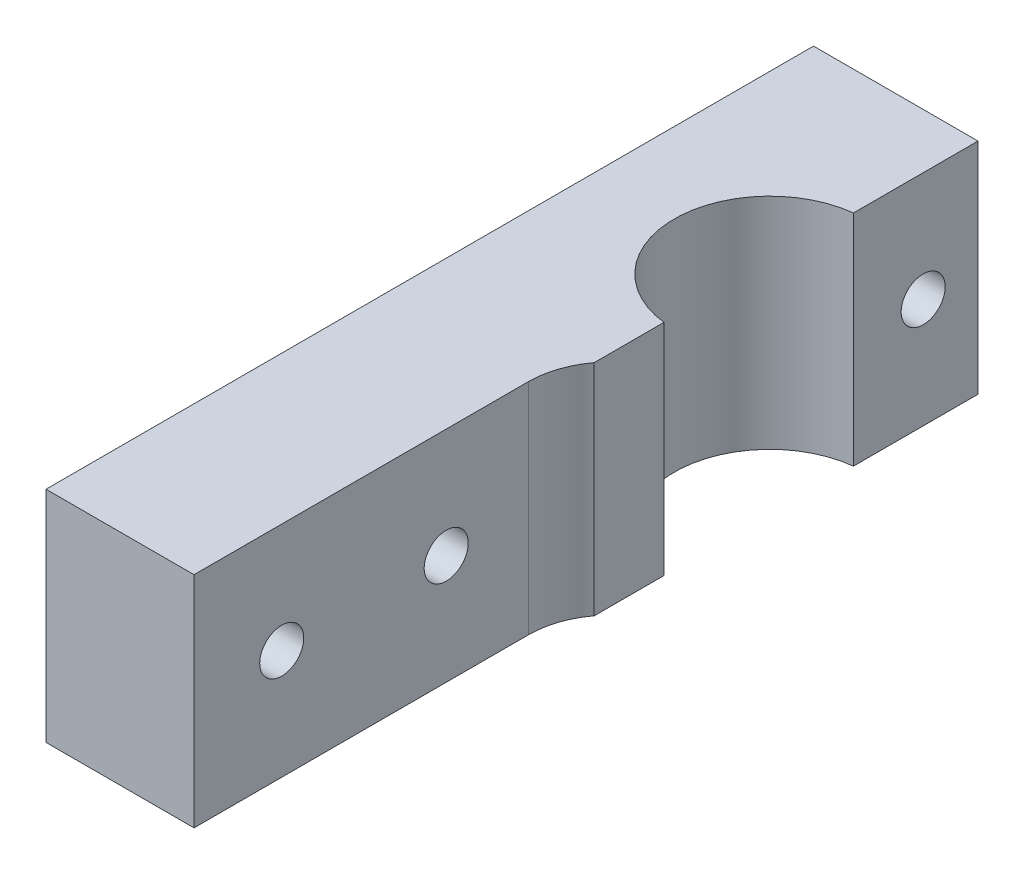
SolidWorks part; units mm, degrees
ref_plane "Front" through (0, 0, 0) normal (0, 0, 1) x (1, 0, 0)
ref_plane "Top" through (0, 0, 0) normal (0, 1, 0) x (1, 0, 0)
ref_plane "Right" through (0, 0, 0) normal (1, 0, 0) x (0, 0, -1)
sketch "Sketch1" plane through (0, 0, 0) normal (0, 1, 0) x (1, 0, 0)
  line L0 (-1.27, 10.9758) -> (-1.27, 25.4)
  line L1 (-1.27, 25.4) -> (-20.32, 25.4)
  line L2 (-1.27, 25.4) -> (-1.27, -63.5) construction
  line L3 (-1.27, -63.5) -> (-20.32, -63.5)
  line L4 (-20.32, 25.4) -> (-20.32, -63.5)
  line L5 (-1.27, -10.9758) -> (-1.27, -63.5)
  arc A0 (-1.27, 10.9758) -> (-1.27, -10.9758) centre (0, 0) ccw
  circle A1 centre (0, 0) radius 11.049 construction
  dimension "D2" = 22.098
  dimension "D1" = 25.4
  dimension "D3" = 19.05
  dimension "D4" = 1.27
  dimension "D5" = 63.5
extrude "Boss-Extrude1" add sketch "Sketch1" along normal mid plane 25.4
sketch "Sketch4" plane through (-20.32, 0, 0) normal (-1, 0, 0) x (0, 0, 1)
  line L0 (63.5, 12.7) -> (63.5, -12.7) construction
  point P0 (-19.05, 0)
  point P1 (34.29, 0)
  point P2 (53.34, 0)
  dimension "D1" = 19.05
  dimension "D2" = 10.16
  dimension "D3" = 19.05
hole_wizard "CBORE for #10 Binding Head Machine Screw1" positions "Sketch5" profile "Sketch6" counterbore size "#10" standard "ANSI Inch"
sketch "Sketch5" plane through (-20.32, 0, 0) normal (-1, 0, 0) x (0, 0, 1)
  point P0 (-19.05, 0)
  point P3 (34.29, 0)
  point P6 (53.34, 0)
sketch "Sketch6" plane through (-20.32, 0, -19.05) normal (0, 1, 0) x (0, 0, 1)
  line L0 (0, 0) -> (0, 509.5338)
  line L1 (0, 509.5338) -> (2.5527, 508)
  line L2 (2.5527, 508) -> (2.5527, 3.1242)
  line L3 (2.5527, 3.1242) -> (5.5562, 3.1242)
  line L4 (5.5562, 3.1242) -> (5.5562, 0)
  line L5 (5.5562, 0) -> (0, 0)
  line L10 (0, 509.5338) -> (-2.5527, 508) construction
  line L11 (0, -6.35) -> (0, 107.95) construction
  dimension "Hole Dia." = 5.1054
  dimension "Hole Depth" = 508
  dimension "C'Bore Dia." = 11.1125
  dimension "C'Bore Depth" = 3.1242
  dimension "Drill Angle" = 118
sketch "Sketch7" plane through (0, 12.7, 0) normal (0, 1, 0) x (1, 0, 0)
  line L1 (-1.27, -63.5) -> (-3.175, -63.5)
  line L2 (-1.27, -63.5) -> (-1.27, -19.05)
  line L3 (-1.27, -19.05) -> (-3.175, -19.05)
  line L4 (-3.175, -63.5) -> (-3.175, -19.05)
  dimension "D1" = 3.175
  dimension "D2" = 44.45
extrude "Cut-Extrude1" cut sketch "Sketch7" against normal through all
fillet "Fillet1" radius 9.525 1 edges at (-3.175, 0, 19.05)
